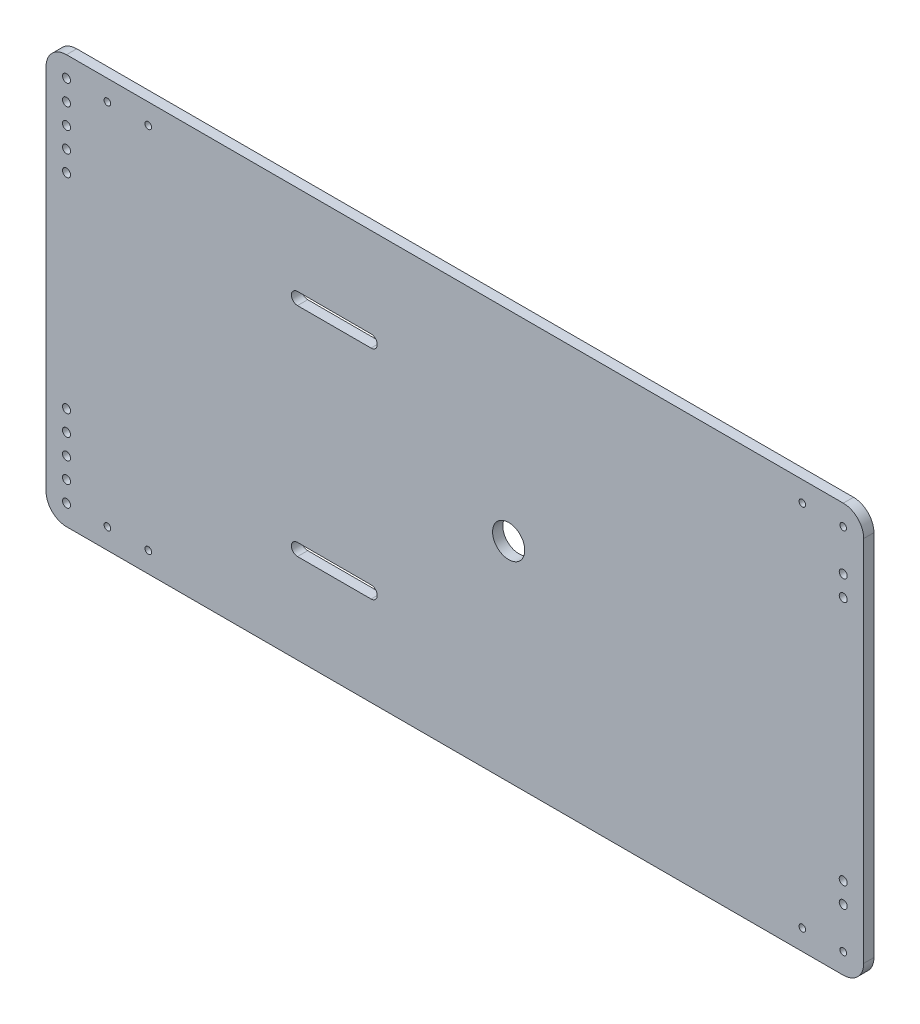
SolidWorks part; units mm, degrees
material "PC High Viscosity"
ref_plane "Front Plane" through (0, 0, 0) normal (0, 0, 1) x (1, 0, 0)
ref_plane "Top Plane" through (0, 0, 0) normal (0, 1, 0) x (1, 0, 0)
ref_plane "Right Plane" through (0, 0, 0) normal (1, 0, 0) x (0, 0, -1)
sketch "Sketch1" plane through (0, 0, 0) normal (0, 0, 1) x (1, 0, 0)
  line L1 (12.7, 0) -> (495.3, 0)
  line L2 (0, 12.7) -> (0, 241.3)
  line L3 (12.7, 254) -> (495.3, 254)
  line L4 (508, 12.7) -> (508, 241.3)
  arc A0 (495.3, 254) -> (508, 241.3) centre (495.3, 241.3) cw
  arc A1 (495.3, 0) -> (508, 12.7) centre (495.3, 12.7) ccw
  arc A2 (12.7, 0) -> (0, 12.7) centre (12.7, 12.7) cw
  arc A3 (0, 241.3) -> (12.7, 254) centre (12.7, 241.3) cw
  point P7 (508, 254)
  point P10 (508, 0)
  point P13 (0, 0)
  point P16 (0, 254)
  dimension "D3" = 12.7
  dimension "D1" = 508
  dimension "D2" = 254
extrude "Boss-Extrude1" add sketch "Sketch1" along normal blind 6.35
sketch "Sketch2" plane through (0, 0, 6.35) normal (0, 0, 1) x (1, 0, 0)
  line L10 (495.3, 254) -> (12.7, 254) construction
  line L11 (0, 241.3) -> (0, 12.7) construction
  line L12 (-20.2403, 127) -> (522.5431, 127) construction
  circle A6 centre (12.7, 190.5) radius 2.5
  circle A7 centre (12.7, 203.2) radius 2.5
  circle A8 centre (12.7, 215.9) radius 2.5
  circle A9 centre (12.7, 228.6) radius 2.5
  circle A10 centre (12.7, 241.3) radius 2.4892
  circle A11 centre (38.1, 241.3) radius 2.0701
  circle A12 centre (63.5, 241.3) radius 2.0701
  circle A13 centre (63.5, 12.7) radius 2.0701
  circle A14 centre (38.1, 12.7) radius 2.0701
  circle A15 centre (12.7, 63.5) radius 2.5
  circle A16 centre (12.7, 50.8) radius 2.5
  circle A17 centre (12.7, 38.1) radius 2.5
  circle A18 centre (12.7, 25.4) radius 2.5
  circle A19 centre (12.7, 12.7) radius 2.4892
  dimension "D2" = 12.7
  dimension "D3" = 5
  dimension "D4" = 4.1402
  dimension "D5" = 4.1402
  dimension "D6" = 4.9784
  dimension "D7" = 5
  dimension "D8" = 5
  dimension "D9" = 5
  dimension "D10" = 12.7
  dimension "D11" = 127
  dimension "D12" = 25.4
  dimension "D13" = 25.4
  dimension "D14" = 12.7
  dimension "D15" = 12.7
  dimension "D16" = 12.7
  dimension "D17" = 12.7
extrude "Cut-Extrude1" cut sketch "Sketch2" against normal through all
sketch "Sketch3" plane through (0, 0, 6.35) normal (0, 0, 1) x (1, 0, 0)
  line L8 (495.3, 254) -> (12.7, 254) construction
  line L11 (508, 12.7) -> (508, 241.3) construction
  line L12 (-50.4543, 127) -> (582.5907, 127) construction
  circle A0 centre (469.8795, 241.3) radius 2.0701
  circle A1 centre (495.2795, 241.3) radius 2.0701
  circle A4 centre (495.2795, 215.9) radius 2.4892
  circle A5 centre (495.2795, 203.2) radius 2.4892
  circle A16 centre (469.8795, 12.7) radius 2.0701
  circle A17 centre (495.2795, 12.7) radius 2.0701
  circle A18 centre (495.2795, 38.1) radius 2.4892
  circle A19 centre (495.2795, 50.8) radius 2.4892
  dimension "D1" = 4.1402
  dimension "D2" = 4.9784
  dimension "D3" = 12.7
  dimension "D4" = 12.7205
  dimension "D5" = 127
  dimension "D10" = 25.4
  dimension "D13" = 25.4
  dimension "D15" = 12.7
extrude "Cut-Extrude2" cut sketch "Sketch3" against normal through all
sketch "Sketch4" plane through (0, 0, 6.35) normal (0, 0, 1) x (1, 0, 0)
  line L0 (495.3, 254) -> (12.7, 254) construction
  line L1 (101.6, 178.054) -> (256.6, 178.054) construction
  line L2 (101.6, 178.054) -> (101.6, 76.054) construction
  line L3 (101.6, 76.054) -> (256.6, 76.054) construction
  line L4 (256.6, 178.054) -> (256.6, 76.054) construction
  line L6 (0, 241.3) -> (0, 12.7) construction
  line L7 (156.21, 194.564) -> (201.93, 194.564) construction
  line L8 (156.21, 198.374) -> (201.93, 198.374)
  line L9 (156.21, 190.754) -> (201.93, 190.754)
  line L10 (156.21, 59.544) -> (201.93, 59.544) construction
  line L11 (156.21, 63.354) -> (201.93, 63.354)
  line L12 (156.21, 55.734) -> (201.93, 55.734)
  arc A0 (156.21, 198.374) -> (156.21, 190.754) centre (156.21, 194.564) ccw
  arc A1 (201.93, 190.754) -> (201.93, 198.374) centre (201.93, 194.564) ccw
  arc A2 (156.21, 63.354) -> (156.21, 55.734) centre (156.21, 59.544) ccw
  arc A3 (201.93, 55.734) -> (201.93, 63.354) centre (201.93, 59.544) ccw
  point P10 (179.07, 194.564)
  point P15 (179.07, 59.544)
  point P22 (0, 0)
  dimension "D7" = 3.81
  dimension "D9" = 3.81
  dimension "D1" = 155
  dimension "D2" = 102
  dimension "D3" = 75.946
  dimension "D4" = 101.6
  dimension "D5" = 77.47
  dimension "D6" = 45.72
  dimension "D8" = 45.72
  dimension "D10" = 12.7
  dimension "D11" = 12.7
extrude "Cut-Extrude3" cut sketch "Sketch4" against normal through all
sketch "Sketch5" plane through (0, 0, 6.35) normal (0, 0, 1) x (1, 0, 0)
  line L0 (307.5263, 284.1622) -> (307.5263, -18.394) construction
  line L1 (508, 12.7) -> (508, 241.3) construction
  line L2 (12.7, 0) -> (495.3, 0) construction
  line L3 (0, 241.3) -> (0, 12.7) construction
  circle A0 centre (287.4065, 129.6573) radius 10
  dimension "D3" = 129.6573
  dimension "15mm" = 20
  dimension "D1" = 200.4737
  dimension "D2" = 302.5562
  dimension "D4" = 287.4065
extrude "Cut-Extrude4" cut sketch "Sketch5" against normal through all
